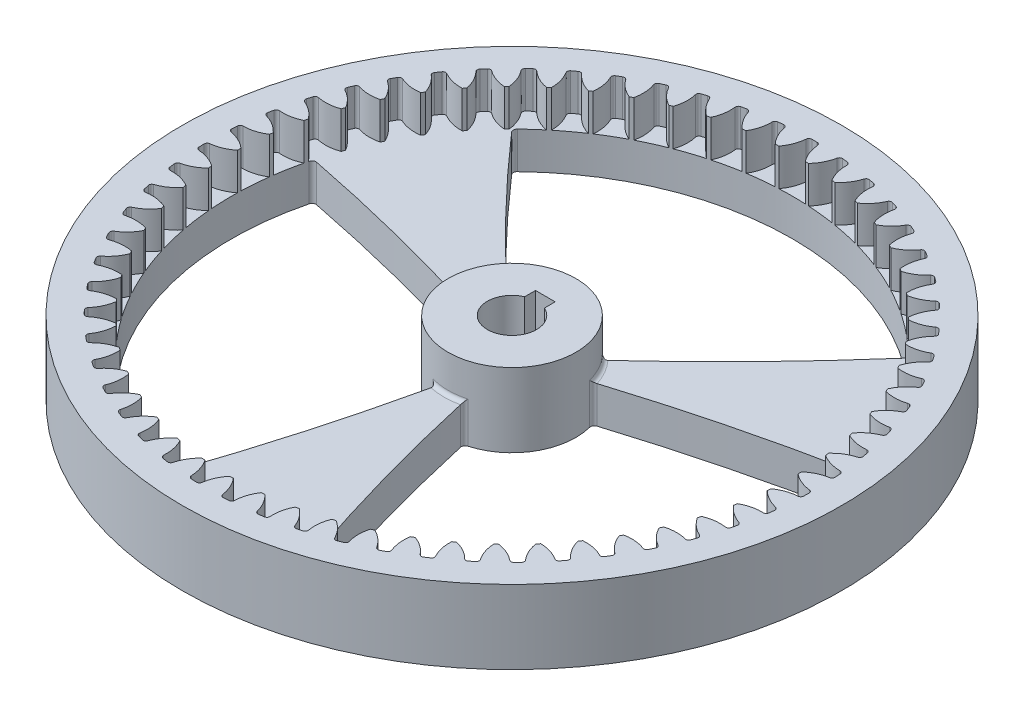
SolidWorks part; units mm, degrees
ref_plane "Plano frontal" through (0, 0, 0) normal (0, 0, 1) x (1, 0, 0)
ref_plane "Plano superior" through (0, 0, 0) normal (0, 1, 0) x (1, 0, 0)
ref_plane "Plano direito" through (0, 0, 0) normal (1, 0, 0) x (0, 0, -1)
sketch "Sketch1" plane through (0, 0, 0) normal (0, 1, 0) x (1, 0, 0)
  circle A0 centre (0, 0) radius 59 construction
  circle A1 centre (0, 0) radius 57
  circle A2 centre (0, 0) radius 61.5
  circle A3 centre (0, 0) radius 67
  dimension "D1" = 118
  dimension "D2" = 114
  dimension "D3" = 123
  dimension "D4" = 134
extrude "Boss-Extrude1" add sketch "Sketch1" along normal blind 7.5 contours A3 A2 | A2 A1 region at (-59.7605, 0, 0) region at (-65.105, 0, 0)
sketch "Sketch2" plane through (0, 7.5, 0) normal (0, 1, 0) x (1, 0, 0)
  line L0 (0, 0) -> (0, 61.5) construction
  line L1 (-1.5706, 58.9791) -> (1.5706, 58.9791) construction
  line L2 (0, 61.5) -> (0, 118) construction
  line L3 (0, 63.2943) -> (-2.6782, 55.9359) construction
  line L4 (0, 0) -> (3.2732, 61.4128) construction
  line L5 (1.5706, 58.9791) -> (4.7074, 58.8119) construction
  line L6 (0, 118) -> (-1.1026, 61.4901) construction
  circle A0 centre (0, 0) radius 57 construction
  circle A1 centre (0, 0) radius 61.5 construction
  circle A2 centre (0, 0) radius 59 construction
  arc A3 (3.0337, 56.9192) -> (-2.6837, 56.9368) centre (0, 0) ccw
  arc A4 (1.1026, 61.4901) -> (-1.1026, 61.4901) centre (0, 0) ccw
  circle A5 centre (0, 0) radius 59 construction
  arc A6 (-1.1026, 61.4901) -> (-3.6496, 55.8809) centre (-8.8869, 61.642) cw
  arc A7 (3.6496, 55.8809) -> (-3.6496, 55.8809) centre (0, 0) ccw
  arc A8 (1.1026, 61.4901) -> (3.6496, 55.8809) centre (8.8869, 61.642) ccw
  circle A9 centre (0, 0) radius 56 construction
  circle A10 centre (0, 0) radius 57 construction
  circle M12 centre (0, 0) radius 57
  dimension "D4" = 118
  dimension "D2" = 20
  dimension "D3" = 3.051
  dimension "D5" = 61.5
  dimension "D1" = 1
extrude "Cut-Extrude1" cut sketch "Sketch2" against normal through all contours A8 A4 A6 M12 region at (0, 7.5, -58.884)
fillet "Fillet1" radius 0.6 2 edges at (1.1026, 3.75, -61.4901) (-1.1026, 3.75, -61.4901)
pattern_circular "CirPattern1" count 59 over 360 about axis through (0, 7.5, 0) along (0, -1, 0) of "Fillet1", "Cut-Extrude1"
sketch "Sketch3" plane through (0, 0, 0) normal (0, -1, 0) x (1, 0, 0)
  circle A0 centre (0, 0) radius 67 construction
  circle A1 centre (0, 0) radius 67
extrude "Boss-Extrude2" add sketch "Sketch3" along normal blind 7.5
sketch "Sketch4" plane through (0, 0, 0) normal (0, 1, 0) x (1, 0, 0)
  line L0 (-2, 6.7826) -> (2, 6.7826)
  line L1 (2, 6.7826) -> (2, 4.5826)
  line L2 (-2, 6.7826) -> (-2, 4.5826)
  arc A0 (-2, 4.5826) -> (2, 4.5826) centre (0, 0) ccw
  circle A1 centre (0, 0) radius 13
  dimension "D1" = 10
  dimension "D2" = 26
  dimension "D3" = 4
  dimension "D4" = 2.2
extrude "Boss-Extrude3" add sketch "Sketch4" along normal up to surface (7.5 mm away) up to face at (0, 7.5, 67)
sketch "Sketch5" plane through (0, 0, 0) normal (0, 1, 0) x (1, 0, 0)
  line L0 (-9.5846, 8.7827) -> (0, 0) construction
  line L1 (0, 0) -> (0, 57) construction
  line L4 (-2, 6.7826) -> (-2, 4.5826) construction
  line L6 (2, 4.5826) -> (2, 6.7826) construction
  line L7 (2, 6.7826) -> (-2, 6.7826) construction
  line L8 (2, 4.5826) -> (2, 6.7826)
  line L9 (2, 6.7826) -> (-2, 6.7826)
  line L10 (-2, 6.7826) -> (-2, 4.5826)
  arc A0 (40.3051, 40.3051) -> (-40.3051, 40.3051) centre (0, 0) ccw
  circle A1 centre (0, 0) radius 13 construction
  arc A2 (9.5846, 8.7827) -> (-9.5846, 8.7827) centre (0, 0) ccw
  arc A3 (2.8137, -12.6918) -> (12.3983, 3.9092) centre (0, 0) ccw
  arc A4 (-40.3051, 40.3051) -> (-9.5846, 8.7827) centre (253.6364, 296.038) ccw
  arc A5 (-2, 4.5826) -> (2, 4.5826) centre (0, 0) ccw construction
  arc A6 (-2, 4.5826) -> (2, 4.5826) centre (0, 0) ccw
  arc A7 (40.3051, 40.3051) -> (9.5846, 8.7827) centre (-253.6364, 296.038) cw
  arc A8 (55.0578, 14.7527) -> (12.3983, 3.9092) centre (129.5582, -367.6746) ccw
  arc A9 (14.7527, -55.0578) -> (55.0578, 14.7527) centre (0, 0) ccw
  arc A10 (14.7527, -55.0578) -> (2.8137, -12.6918) centre (383.1947, 71.6366) cw
  arc A11 (-12.3983, 3.9092) -> (-2.8137, -12.6918) centre (0, 0) ccw
  arc A12 (-14.7527, -55.0578) -> (-2.8137, -12.6918) centre (-383.1947, 71.6366) ccw
  arc A13 (-55.0578, 14.7527) -> (-14.7527, -55.0578) centre (0, 0) ccw
  arc A14 (-55.0578, 14.7527) -> (-12.3983, 3.9092) centre (-129.5582, -367.6746) cw
  point P31 (0, 0)
  dimension "D1" = 114
  dimension "D2" = 95
  dimension "D3" = 90
  dimension "D4" = 3
extrude "Cut-Extrude2" cut sketch "Sketch5" against normal blind 10
fillet "Fillet2" radius 0.8 15 edges at (14.7527, -3.75, 55.0578) (-14.7527, -3.75, 55.0578) (-2.8137, -3.75, 12.6918) (0, 0, 13) (2.8137, -3.75, 12.6918) (55.0578, -3.75, -14.7527) (40.3051, -3.75, -40.3051) (12.3983, -3.75, -3.9092) (9.5846, -3.75, -8.7827) (11.2583, 0, -6.5) (-9.5846, -3.75, -8.7827) (-11.2583, 0, -6.5) (-12.3983, -3.75, -3.9092) (-55.0578, -3.75, -14.7527) (-40.3051, -3.75, -40.3051)
